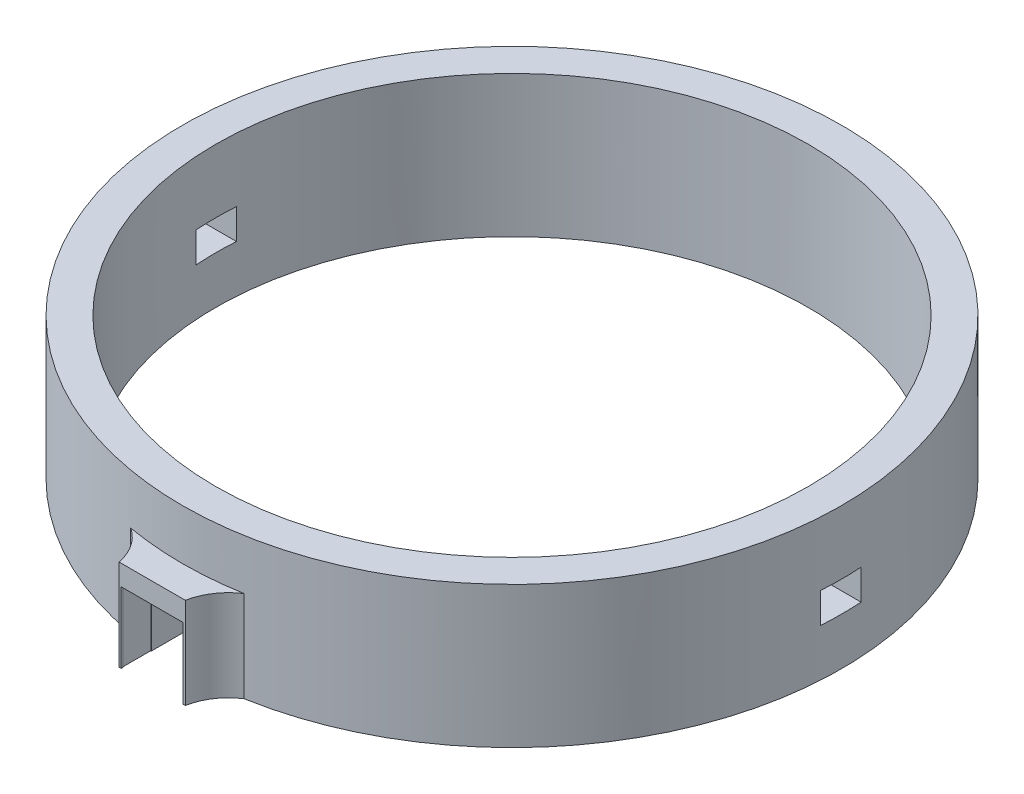
SolidWorks part; units mm, degrees
ref_plane "Front Plane" through (0, 0, 0) normal (0, 0, 1) x (1, 0, 0)
ref_plane "Top Plane" through (0, 0, 0) normal (0, 1, 0) x (1, 0, 0)
ref_plane "Right Plane" through (0, 0, 0) normal (1, 0, 0) x (0, 0, -1)
sketch "Sketch1" plane through (0, 0, 0) normal (0, 1, 0) x (1, 0, 0)
  circle A0 centre (0, 0) radius 9945.7494
  circle A1 centre (0, 0) radius 9500
  dimension "D1" = 19891.4989
  dimension "D2" = 19000
extrude "Boss-Extrude1" add sketch "Sketch1" along normal blind 4267.2 contours A0
sketch "Sketch2" plane through (0, 4267.2, 0) normal (0, 1, 0) x (1, 0, 0)
  circle A0 centre (0, 0) radius 8945.7494
  circle A1 centre (0, 0) radius 9945.7494 construction
  dimension "D1" = 1000
extrude "Cut-Extrude1" cut sketch "Sketch2" against normal blind 4267.2 contours A0
ref_plane "Plane2" through (0, 0, 9945.7494) normal (0, 0, 1) x (1, 0, 0)
sketch "Sketch4" plane through (0, 0, 9945.7494) normal (0, 0, 1) x (1, 0, 0)
  line L0 (0, -2346.96) -> (0, 2346.96) construction
  line L1 (1000, 0) -> (-1000, 0)
  line L2 (1000, 0) -> (1000, 2750)
  line L3 (1000, 2750) -> (-1000, 2750)
  line L4 (-1000, 0) -> (-1000, 2750)
  line L5 (1000, 0) -> (-1000, 2750) construction
  line L6 (1000, 2750) -> (-1000, 0) construction
  line L7 (10940.3244, 0) -> (-10940.3244, 0) construction
  point P0 (0, 1375)
  dimension "D1" = 2750
  dimension "D2" = 2000
extrude "Boss-Extrude2" add sketch "Sketch4" along normal blind 914.4 separate body
sketch "Sketch5" plane through (0, 0, 10860.1494) normal (0, 0, 1) x (1, 0, 0)
  line L0 (0, -2346.96) -> (0, 2346.96) construction
  line L1 (935, 0) -> (-935, 0)
  line L2 (935, 0) -> (935, 2135)
  line L3 (935, 2135) -> (-935, 2135)
  line L4 (-935, 0) -> (-935, 2135)
  line L5 (935, 0) -> (-935, 2135) construction
  line L6 (935, 2135) -> (-935, 0) construction
  line L7 (-1000, 0) -> (1000, 0) construction
  point P0 (0, 1067.5)
  dimension "D1" = 1870
  dimension "D2" = 2135
extrude "Cut-Extrude2" cut sketch "Sketch5" against normal mid plane 5000
sketch "Sketch6" plane through (-935, 0, 0) normal (1, 0, 0) x (0, 0, -1)
  line L0 (-10860.1494, 2135) -> (-10860.1494, 0) construction
  line L1 (-9945.7494, -75.4869) -> (-10810.1494, -75.4869)
  line L2 (-9945.7494, -75.4869) -> (-9945.7494, 2147.3115)
  line L3 (-9945.7494, 2147.3115) -> (-10810.1494, 2147.3115)
  line L4 (-10810.1494, -75.4869) -> (-10810.1494, 2147.3115)
  line L5 (-9945.7494, -75.4869) -> (-10810.1494, 2147.3115) construction
  line L6 (-9945.7494, 2147.3115) -> (-10810.1494, -75.4869) construction
  line L7 (-9945.7494, 2346.96) -> (-9945.7494, -2346.96) construction
  point P0 (-10377.9494, 1035.9123)
  dimension "D1" = 50
extrude "Cut-Extrude3" cut sketch "Sketch6" against normal blind 16.77
mirror "Mirror1" about plane through (0, 0, 0) normal (1, 0, 0) of "Cut-Extrude3"
sketch "Sketch7" plane through (0, 2135, 0) normal (0, -1, 0) x (1, 0, 0)
  line L0 (0, -2346.96) -> (0, 2346.96) construction
  line L1 (943.385, 10041.4502) -> (-943.385, 10041.4502)
  line L2 (943.385, 10041.4502) -> (943.385, 10810.1494)
  line L3 (943.385, 10810.1494) -> (-943.385, 10810.1494)
  line L4 (-943.385, 10041.4502) -> (-943.385, 10810.1494)
  line L5 (943.385, 10041.4502) -> (-943.385, 10810.1494) construction
  line L6 (943.385, 10810.1494) -> (-943.385, 10041.4502) construction
  line L7 (-951.77, 10810.1494) -> (-935, 10810.1494) construction
  line L8 (935, 10860.1494) -> (-935, 10860.1494) construction
  point P0 (0, 10425.7998)
  dimension "D1" = 50
extrude "Cut-Extrude4" cut sketch "Sketch7" against normal blind 16.77
sketch "Sketch8" plane through (0, 0, 0) normal (0, 1, 0) x (1, 0, 0)
  line L1 (-2346.96, -9945.7494) -> (2346.96, -9945.7494) construction
  line L2 (-1000, -10860.1494) -> (-1000, -9945.7494) construction
  line L3 (-1000, -9945.7494) -> (-1000, -10860.1494)
  line L4 (0, -2346.96) -> (0, 2346.96) construction
  line L5 (1000, -9945.7494) -> (1000, -10860.1494)
  line L6 (-1000, -9895.349) -> (1000, -9895.349)
  line L7 (1000, -9945.7494) -> (-1000, -9945.7494)
  circle A0 centre (0, 0) radius 9945.7494 construction
  arc A1 (-1000, -10860.1494) -> (-1709.7578, -9797.6865) centre (-2617.2235, -11172.2028) ccw
  arc A2 (-1709.7578, -9797.6865) -> (-1000, -9895.349) centre (0, 0) ccw
  arc A3 (1000, -10860.1494) -> (1709.7578, -9797.6865) centre (2617.2235, -11172.2028) cw
  arc A4 (1709.7578, -9797.6865) -> (1000, -9895.349) centre (0, 0) cw
extrude "Boss-Extrude3" add sketch "Sketch8" along normal up to surface (2750 mm away) up to face at (0, 2750, 10402.9494)
sketch "Sketch9" plane through (0, 0, 9945.7494) normal (0, 0, 1) x (1, 0, 0)
  line L1 (926.615, -141.7417) -> (-935, -141.7417)
  line L2 (926.615, -141.7417) -> (926.615, 2135)
  line L3 (926.615, 2135) -> (-935, 2135)
  line L4 (-935, -141.7417) -> (-935, 2135)
  line L5 (926.615, -141.7417) -> (-935, 2135) construction
  line L6 (926.615, 2135) -> (-935, -141.7417) construction
  point P0 (-4.1925, 996.6291)
extrude "Cut-Extrude5" cut sketch "Sketch9" against normal blind 4000
sketch "Sketch10" plane through (0, 0, 0) normal (1, 0, 0) x (0, 0, -1)
  line L0 (0, 2424.9179) -> (0, -2424.9179) construction
  line L1 (609.6, 1430.1679) -> (-609.6, 1430.1679)
  line L2 (609.6, 1430.1679) -> (609.6, 2344.5679)
  line L3 (609.6, 2344.5679) -> (-609.6, 2344.5679)
  line L4 (-609.6, 1430.1679) -> (-609.6, 2344.5679)
  line L5 (609.6, 1430.1679) -> (-609.6, 2344.5679) construction
  line L6 (609.6, 2344.5679) -> (-609.6, 1430.1679) construction
  point P0 (0, 1887.3679)
  dimension "D1" = 914.4
  dimension "D2" = 90
  dimension "D3" = 1219.2
extrude "Cut-Extrude6" cut sketch "Sketch10" against normal through all both and the other way through all
